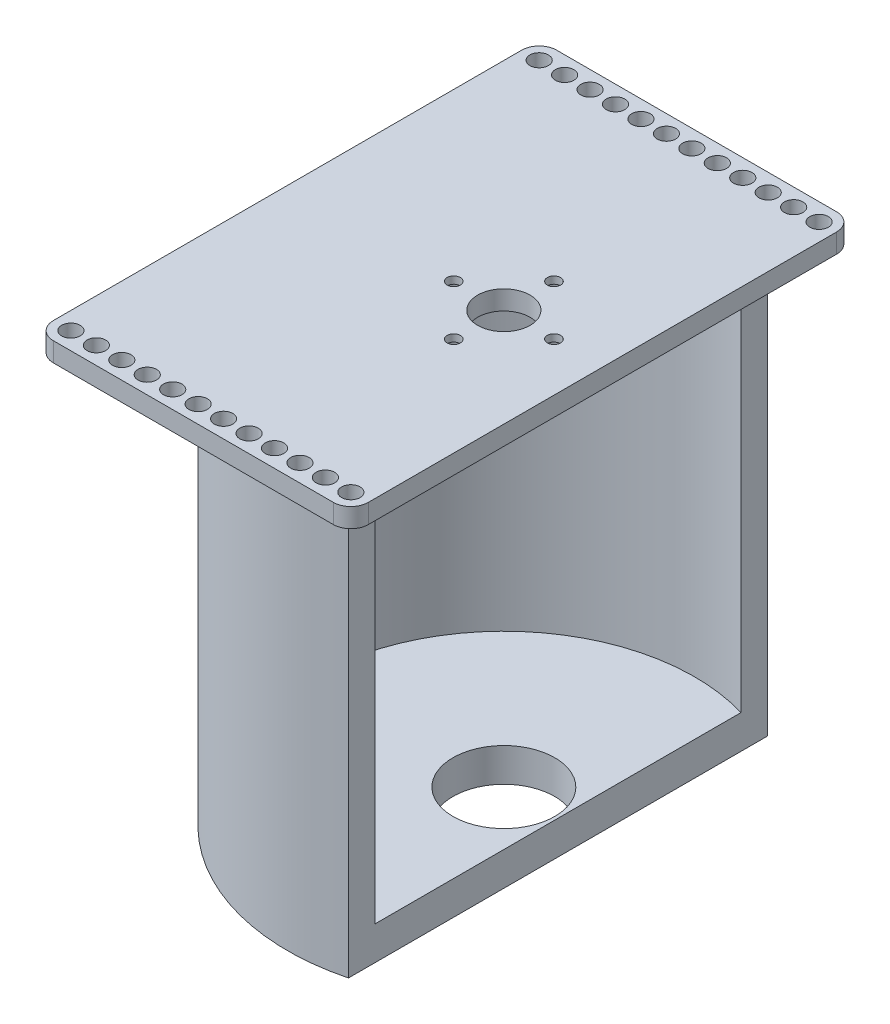
SolidWorks part; units mm, degrees
note: The reader was unsure of these and kept them because the rebuilt part matched: shared geometry of "Sketch3<3>".
ref_plane "Front Plane" through (0, 0, 0) normal (0, 0, 1) x (1, 0, 0)
ref_plane "Top Plane" through (0, 0, 0) normal (0, 1, 0) x (1, 0, 0)
ref_plane "Right Plane" through (0, 0, 0) normal (1, 0, 0) x (0, 0, -1)
sketch "Sketch1" plane through (0, 0, 0) normal (0, 1, 0) x (1, 0, 0)
  circle A0 centre (0, 0) radius 53.975
  circle A2 centre (0, 0) radius 12.7
  dimension "D1" = 25.4
  dimension "D2" = 107.95
extrude "Boss-Extrude1" add sketch "Sketch1" along normal blind 8.382
sketch "Sketch3" plane through (0, 8.382, 0) normal (0, 1, 0) x (1, 0, 0)
  line L5 (13.4938, 52.2611) -> (13.4938, -52.2611)
  arc A0 (13.4938, 52.2611) -> (13.4938, -52.2611) centre (0, 0) ccw
  circle A1 centre (0, 0) radius 53.975 construction
  arc A2 (13.4938, 45.6734) -> (13.4938, -45.6734) centre (0, 0) ccw
  dimension "D1" = 6.35
  dimension "D2" = 13.4937
  dimension "D3" = 91.3468
extrude "Boss-Extrude2" add sketch "Sketch3" along normal blind 98.2345
sketch "Sketch6" plane through (0, 106.6165, 0) normal (0, 1, 0) x (1, 0, 0)
  line L1 (0, 12.5) -> (-12.5, 0) construction
  line L2 (-12.5, 0) -> (0, -12.5) construction
  line L3 (0, -12.5) -> (12.5, 0) construction
  line L4 (12.5, 0) -> (0, 12.5) construction
  circle A0 centre (0, 0) radius 12.5 construction
  circle A1 centre (0, 0) radius 6.55
  circle A2 centre (0, 0) radius 53.975
  arc A3 (13.4938, 52.2611) -> (13.4938, -52.2611) centre (0, 0) ccw construction
  dimension "D1" = 13.1
  dimension "D2" = 25
extrude "Boss-Extrude6" add sketch "Sketch6" along normal blind 4.8
hole_wizard "CBORE for M3 SHCS1" positions "Sketch7" profile "Sketch8" counterbore size "M3" standard "ANSI Metric"
sketch "Sketch7" plane through (0, 106.6165, 0) normal (0, -1, 0) x (-1, 0, 0)
  point P0 (-12.5, 0)
  point P3 (0, -12.5)
  point P6 (0, 12.5)
  point P9 (12.5, 0)
sketch "Sketch8" plane through (12.5, 106.6165, 0) normal (1, 0, 0) x (0, 0, -1)
  line L0 (0, 0) -> (0, 4.8)
  line L1 (0, 4.8) -> (1.65, 4.8)
  line L3 (1.65, 4.8) -> (1.65, 3)
  line L4 (1.65, 3) -> (3.25, 3)
  line L5 (3.25, 3) -> (3.25, 0)
  line L7 (3.25, 0) -> (0, 0)
  line L11 (0, -6.35) -> (0, 107.95) construction
  dimension "Thru Hole Dia." = 3.3
  dimension "Thru Hole Depth" = 4.8
  dimension "C'Bore Dia." = 6.5
  dimension "C'Bore Depth" = 3
extrude "Cut-Extrude2" cut sketch "Sketch3<3>" against normal through all
sketch "Sketch3<3>" plane through (0, 8.382, 0) normal (0, 1, 0) x (1, 0, 0) same geometry as "Sketch3"
sketch "Sketch10" plane through (0, 111.4165, 0) normal (0, 1, 0) x (1, 0, 0)
  line L0 (-53.975, 0) -> (-53.975, 58.42)
  line L1 (-49.6094, 62.7856) -> (20.2406, 62.7856)
  line L2 (24.6062, 58.42) -> (24.6062, 0)
  line L3 (24.6062, 0) -> (-53.975, 0)
  circle A57 centre (-49.6094, 58.42) radius 2.3114
  circle A58 centre (-43.2594, 58.42) radius 2.3114
  circle A59 centre (-36.9094, 58.42) radius 2.3114
  circle A60 centre (-30.5594, 58.42) radius 2.3114
  circle A61 centre (-24.2094, 58.42) radius 2.3114
  circle A62 centre (-17.8594, 58.42) radius 2.3114
  circle A63 centre (-11.5094, 58.42) radius 2.3114
  circle A64 centre (-5.1594, 58.42) radius 2.3114
  circle A65 centre (1.1906, 58.42) radius 2.3114
  circle A66 centre (7.5406, 58.42) radius 2.3114
  circle A69 centre (0, 0) radius 53.975 construction
  arc A70 (-53.975, 58.42) -> (-49.6094, 62.7856) centre (-49.6094, 58.42) cw
  circle A72 centre (13.8906, 58.42) radius 2.3114
  circle A73 centre (20.2406, 58.42) radius 2.3114
  arc A74 (20.2406, 62.7856) -> (24.6062, 58.42) centre (20.2406, 58.42) cw
  dimension "D1" = 4.6228
  dimension "D4" = 4.3656
  dimension "D5" = 58.42
  dimension "D3" = 6.35
  dimension "D2" = 12
extrude "Boss-Extrude7" add sketch "Sketch10" against normal up to surface (4.8 mm away)
mirror "Mirror1" about plane through (0, 0, 0) normal (0, 0, 1) of "Boss-Extrude7"
sketch "Sketch11" plane through (0, 111.4165, 0) normal (0, 1, 0) x (1, 0, 0)
  line L1 (24.6062, 48.0399) -> (53.975, 48.0399)
  line L2 (24.6062, 48.0399) -> (24.6062, -48.0399)
  line L3 (24.6062, -48.0399) -> (53.975, -48.0399)
  line L4 (53.975, 48.0399) -> (53.975, -48.0399)
  arc A0 (24.6062, -48.0399) -> (24.6062, 48.0399) centre (0, 0) ccw construction
extrude "Cut-Extrude3" cut sketch "Sketch11" against normal through all
